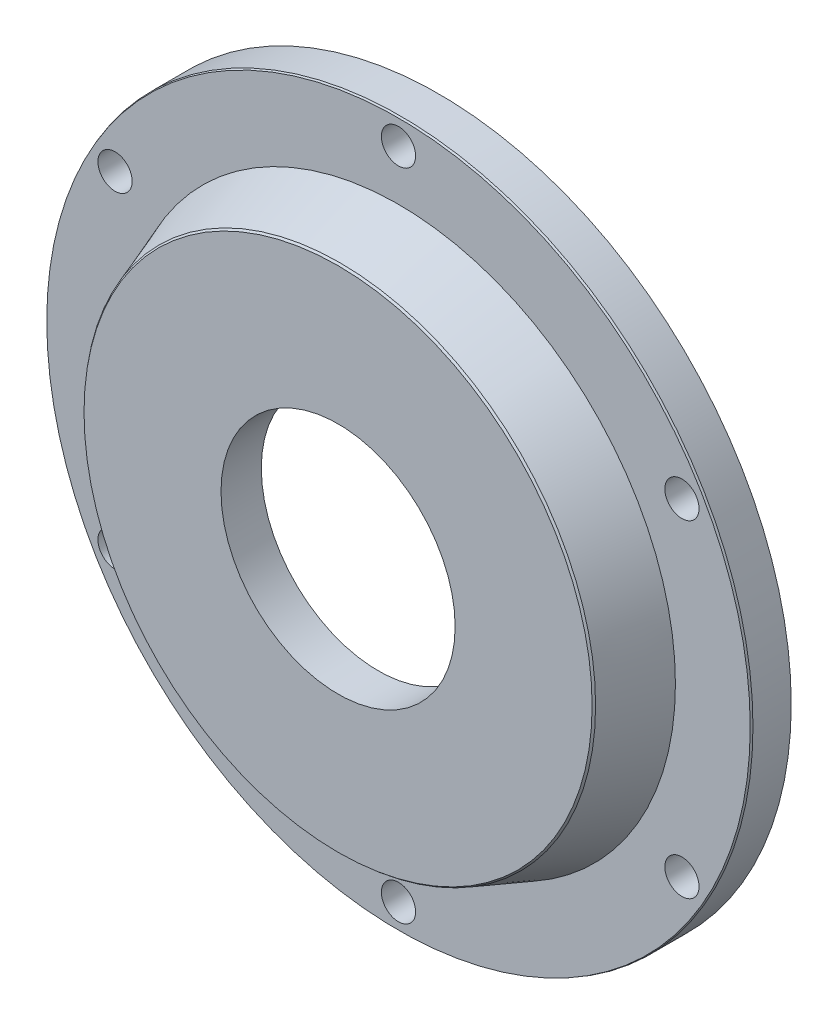
SolidWorks part; units mm, degrees
ref_plane "Front Plane" through (0, 0, 0) normal (0, 0, 1) x (1, 0, 0)
ref_plane "Top Plane" through (0, 0, 0) normal (0, 1, 0) x (1, 0, 0)
ref_plane "Right Plane" through (0, 0, 0) normal (1, 0, 0) x (0, 0, -1)
sketch "Sketch1" plane through (0, 0, 0) normal (0, 0, 1) x (1, 0, 0)
  circle A0 centre (0, 0) radius 35
  dimension "D1" = 70
extrude "Boss-Extrude1" add sketch "Sketch1" against normal blind 10
sketch "Sketch2" plane through (0, 0, -10) normal (0, 0, -1) x (-1, 0, 0)
  circle A0 centre (0, 0) radius 26.5
  dimension "D1" = 53
extrude "Cut-Extrude1" cut sketch "Sketch2" against normal blind 6
sketch "Sketch4" plane through (0, 0, -10) normal (0, 0, -1) x (-1, 0, 0)
  circle A0 centre (0, 0) radius 30
  dimension "D1" = 60
chamfer "Chamfer1" distance 3.5 angle 45 1 edges at (-26.5, 0, -10)
sketch "Sketch5" plane through (0, 0, 0) normal (0, 0, 1) x (1, 0, 0)
  circle A0 centre (0, 0) radius 27.5
  circle A1 centre (0, 0) radius 35
  dimension "D1" = 55
  dimension "D2" = 70
extrude "Cut-Extrude3" cut sketch "Sketch5" against normal blind 6
chamfer "Chamfer3" distance 6 angle 20 1 edges at (27.5, 0, 0) first distance on face at (27.5, 0, -6)
sketch "Sketch6" plane through (0, 0, 0) normal (0, 0, 1) x (1, 0, 0)
  circle A0 centre (0, 0) radius 11.625
  dimension "D1" = 23.25
extrude "Cut-Extrude4" cut sketch "Sketch6" against normal blind 6
sketch "Sketch8" plane through (0, 0, -6) normal (0, 0, 1) x (1, 0, 0)
  line L0 (0, 0) -> (0, 32.5)
  circle A0 centre (0, 0) radius 32.5
  dimension "D1" = 65
hole_wizard "M3 Clearance Hole1" positions "3DSketch1" profile "Sketch9" hole size "M3" standard "ISO" end condition up to next
sketch3d "3DSketch1"
  point P0 (0, 32.5, -6)
sketch "Sketch9" plane through (0, 32.5, -6) normal (1, 0, 0) x (0, -1, 0)
  line L0 (0, 0) -> (0, 4)
  line L1 (0, 4) -> (1.7, 4)
  line L2 (1.7, 4) -> (1.7, 0)
  line L5 (1.7, 0) -> (0, 0)
  line L11 (0, -6.35) -> (0, 107.95) construction
  dimension "Thru Hole Dia." = 3.4
  dimension "Thru Hole Depth" = 4
pattern_circular "CirPattern1" count 6 over 360 about axis through (0, 0, -6) along (0, 0, 1) of "M3 Clearance Hole1"
chamfer "Chamfer4" distance 0.2 angle 20 2 edges at (25.3162, 0, 0) (35, 0, -6) first distance on face at (27.5, 0, -6) first distance on face at (35, 0, -10)
